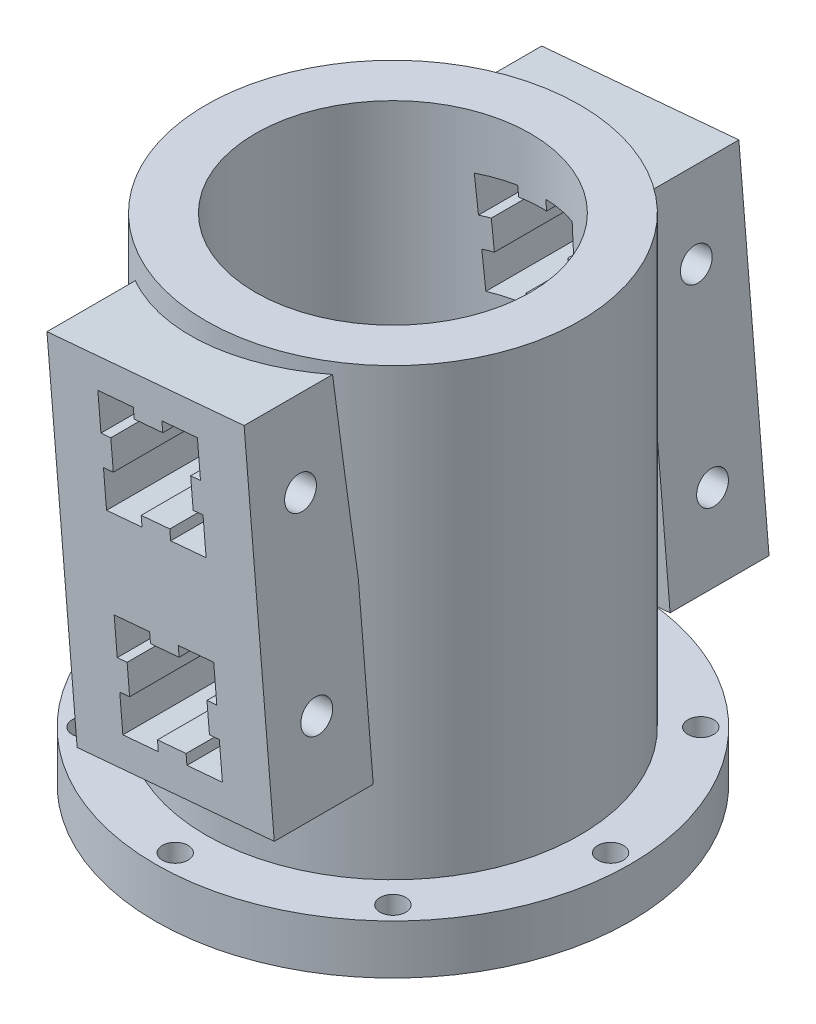
SolidWorks part; units mm, degrees
ref_plane "Front Plane" through (0, 0, 0) normal (0, 0, 1) x (1, 0, 0)
ref_plane "Top Plane" through (0, 0, 0) normal (0, 1, 0) x (1, 0, 0)
ref_plane "Right Plane" through (0, 0, 0) normal (1, 0, 0) x (0, 0, -1)
ref_axis "Axe1" through (0, -1.825, 0) along (0, 1, 0)
sketch "Esquisse1" plane through (0, 0, 0) normal (0, 0, 1) x (1, 0, 0)
  line L0 (13.9, 0) -> (13.9, 50)
  line L1 (13.9, 50) -> (18.9, 50)
  line L4 (18.9, 50) -> (18.9, 5)
  line L5 (18.9, 5) -> (24, 5)
  line L6 (24, 5) -> (24, 0)
  line L7 (24, 0) -> (13.9, 0)
  line L8 (0, -1.825) -> (0, 38.325) construction
  point P2 (18.9, 45)
  point P11 (18.9, 46.1608)
  dimension "D1" = 13.9
  dimension "D4" = 5
  dimension "D5" = 24
  dimension "D6" = 5
  dimension "D7" = 50
revolve "Révolution1" add sketch "Esquisse1" angle 360 about axis through (0, -1.825, 0) along (0, 1, 0)
sketch "Esquisse4" plane through (0, 0, 0) normal (0, -1, 0) x (-1, 0, 0)
  circle A0 centre (0, -22) radius 1.3
  dimension "D1" = 2.6
  dimension "D2" = 22
extrude "FixingHole" cut sketch "Esquisse4" against normal through all
pattern_circular "FixingHoleRepetition" count 8 over 360 about axis through (0, -1.825, 0) along (0, 1, 0) of "FixingHole"
ref_plane "Plan1" through (0, 0, 15) normal (0, 0, 1) x (1, 0, 0)
sketch "Esquisse5" plane through (0, 0, 15) normal (0, 0, 1) x (1, 0, 0)
  line L0 (9.9619, 48.8716) -> (13.0124, 14.0047)
  line L1 (13.0124, 14.0047) -> (-6.9115, 12.2616)
  line L2 (-6.9115, 12.2616) -> (-9.9619, 47.1284)
  line L3 (-9.9619, 47.1284) -> (9.9619, 48.8716)
  line L4 (0, -1.825) -> (0, 38.325) construction
  line L5 (6.8897, 26.6191) -> (7.2034, 23.0328)
  line L6 (18.9, 50) -> (-18.9, 50) construction
  line L7 (5.2424, 45.4472) -> (5.5562, 41.8609)
  line L8 (5.5562, 41.8609) -> (4.56, 41.7737)
  line L9 (4.56, 41.7737) -> (4.8128, 38.8848)
  line L10 (4.8128, 38.8848) -> (5.809, 38.9719)
  line L11 (5.809, 38.9719) -> (6.1227, 35.3856)
  line L12 (6.1227, 35.3856) -> (2.5364, 35.0719)
  line L13 (2.5364, 35.0719) -> (2.4493, 36.0681)
  line L14 (2.4493, 36.0681) -> (-0.4397, 35.8153)
  line L15 (-0.4397, 35.8153) -> (-0.3526, 34.8191)
  line L16 (-0.3526, 34.8191) -> (-3.9389, 34.5054)
  line L17 (-3.9389, 34.5054) -> (-4.2526, 38.0917)
  line L18 (-4.2526, 38.0917) -> (-3.2564, 38.1788)
  line L19 (-3.2564, 38.1788) -> (-3.5092, 41.0678)
  line L20 (-3.5092, 41.0678) -> (-4.5054, 40.9806)
  line L21 (-4.5054, 40.9806) -> (-4.8191, 44.5669)
  line L22 (-4.8191, 44.5669) -> (-1.2328, 44.8807)
  line L23 (-1.2328, 44.8807) -> (-1.1457, 43.8845)
  line L24 (-1.1457, 43.8845) -> (1.7433, 44.1372)
  line L25 (1.7433, 44.1372) -> (1.6561, 45.1334)
  line L26 (1.6561, 45.1334) -> (5.2424, 45.4472)
  line L27 (7.2034, 23.0328) -> (6.2073, 22.9457)
  line L28 (6.2073, 22.9457) -> (6.46, 20.0567)
  line L29 (6.46, 20.0567) -> (7.4562, 20.1438)
  line L30 (7.4562, 20.1438) -> (7.77, 16.5575)
  line L31 (7.77, 16.5575) -> (4.1837, 16.2438)
  line L32 (4.1837, 16.2438) -> (4.0965, 17.24)
  line L33 (4.0965, 17.24) -> (1.2075, 16.9872)
  line L34 (1.2075, 16.9872) -> (1.2947, 15.991)
  line L35 (1.2947, 15.991) -> (-2.2916, 15.6773)
  line L36 (-2.2916, 15.6773) -> (-2.6054, 19.2636)
  line L37 (-2.6054, 19.2636) -> (-1.6092, 19.3507)
  line L38 (-1.6092, 19.3507) -> (-1.8619, 22.2397)
  line L39 (-1.8619, 22.2397) -> (-2.8581, 22.1525)
  line L40 (-2.8581, 22.1525) -> (-3.1719, 25.7388)
  line L41 (-3.1719, 25.7388) -> (0.4144, 26.0526)
  line L42 (0.4144, 26.0526) -> (0.5016, 25.0564)
  line L43 (0.5016, 25.0564) -> (3.3905, 25.3092)
  line L44 (3.3905, 25.3092) -> (3.3034, 26.3054)
  line L45 (3.3034, 26.3054) -> (6.8897, 26.6191)
  point P6 (0, 48)
  point P49 (7.5976, 15.6063)
  point P50 (6.6483, 25.6731)
  point P51 (5.974, 22.283)
  point P52 (5.8002, 18.084)
  dimension "D1" = 5
  dimension "D2" = 35
  dimension "D3" = 2
  dimension "D4" = 20
  dimension "D5" = 10.1
  dimension "D6" = 5
  dimension "D7" = 3
  dimension "D8" = 1
  dimension "D9" = 3.6
  dimension "D10" = 10.1
  dimension "D11" = 3.6
  dimension "D12" = 2.9
  dimension "D13" = 3
extrude "RightFixing" add sketch "Esquisse5" along normal blind 10
sketch "Esquisse7" plane through (14.1295, 1.2362, 0) normal (0.9962, 0.0872, 0) x (0, 0, -1)
  line L0 (-25, 47.8173) -> (-16.0614, 47.8173) construction
  line L1 (-25, 12.8173) -> (-25, 47.8173) construction
  line L2 (-25, 12.8173) -> (-15, 12.8173) construction
  circle A0 centre (-20, 39.7673) radius 1.6
  circle A1 centre (-20, 20.9673) radius 1.6
  dimension "D1" = 8.05
  dimension "D3" = 3.2
  dimension "D2" = 5
  dimension "D4" = 8.15
  dimension "D5" = 5
extrude "TopFixingHoles" cut sketch "Esquisse7" against normal up to next
mirror "FixingSymetry" about plane through (0, 0, 0) normal (0, 0, 1) of "TopFixingHoles", "RightFixing"
sketch "Esquisse6" plane through (0, 0, 25) normal (0, 0, 1) x (1, 0, 0)
  line L0 (5.2424, 45.4472) -> (5.5562, 41.8609)
  line L1 (5.5562, 41.8609) -> (4.56, 41.7737)
  line L2 (4.8128, 38.8848) -> (4.56, 41.7737) construction
  line L3 (4.56, 41.7737) -> (4.8128, 38.8848)
  line L4 (5.809, 38.9719) -> (4.8128, 38.8848) construction
  line L5 (4.8128, 38.8848) -> (5.809, 38.9719)
  line L6 (5.809, 38.9719) -> (6.1227, 35.3856)
  line L7 (6.1227, 35.3856) -> (2.5364, 35.0719)
  line L8 (2.5364, 35.0719) -> (2.4493, 36.0681)
  line L9 (2.4493, 36.0681) -> (-0.4397, 35.8153)
  line L10 (-0.4397, 35.8153) -> (-0.3526, 34.8191)
  line L11 (-0.3526, 34.8191) -> (-3.9389, 34.5054)
  line L12 (-3.9389, 34.5054) -> (-4.2526, 38.0917)
  line L13 (-4.2526, 38.0917) -> (-3.2564, 38.1788)
  line L14 (-3.2564, 38.1788) -> (-3.5092, 41.0678)
  line L15 (-3.5092, 41.0678) -> (-4.5054, 40.9806)
  line L16 (-4.5054, 40.9806) -> (-4.8191, 44.5669)
  line L17 (-4.8191, 44.5669) -> (-1.2328, 44.8807)
  line L18 (-1.2328, 44.8807) -> (-1.1457, 43.8845)
  line L19 (-1.1457, 43.8845) -> (1.7433, 44.1372)
  line L20 (1.7433, 44.1372) -> (1.6561, 45.1334)
  line L21 (1.6561, 45.1334) -> (5.2424, 45.4472)
  line L22 (6.8897, 26.6191) -> (7.2034, 23.0328)
  line L23 (7.2034, 23.0328) -> (6.2073, 22.9457)
  line L24 (6.2073, 22.9457) -> (6.46, 20.0567)
  line L25 (6.46, 20.0567) -> (7.4562, 20.1438)
  line L26 (7.4562, 20.1438) -> (7.77, 16.5575)
  line L27 (7.77, 16.5575) -> (4.1837, 16.2438)
  line L28 (4.1837, 16.2438) -> (4.0965, 17.24)
  line L29 (4.0965, 17.24) -> (1.2075, 16.9872)
  line L30 (1.2075, 16.9872) -> (1.2947, 15.991)
  line L31 (1.2947, 15.991) -> (-2.2916, 15.6773)
  line L32 (-2.2916, 15.6773) -> (-2.6054, 19.2636)
  line L33 (-2.6054, 19.2636) -> (-1.6092, 19.3507)
  line L34 (-1.6092, 19.3507) -> (-1.8619, 22.2397)
  line L35 (-1.8619, 22.2397) -> (-2.8581, 22.1525)
  line L36 (-2.8581, 22.1525) -> (-3.1719, 25.7388)
  line L37 (-3.1719, 25.7388) -> (0.4144, 26.0526)
  line L38 (0.4144, 26.0526) -> (0.5016, 25.0564)
  line L39 (0.5016, 25.0564) -> (3.3905, 25.3092)
  line L40 (3.3905, 25.3092) -> (3.3034, 26.3054)
  line L41 (3.3034, 26.3054) -> (6.8897, 26.6191)
extrude "HoleForFixing" cut sketch "Esquisse6" against normal through all
